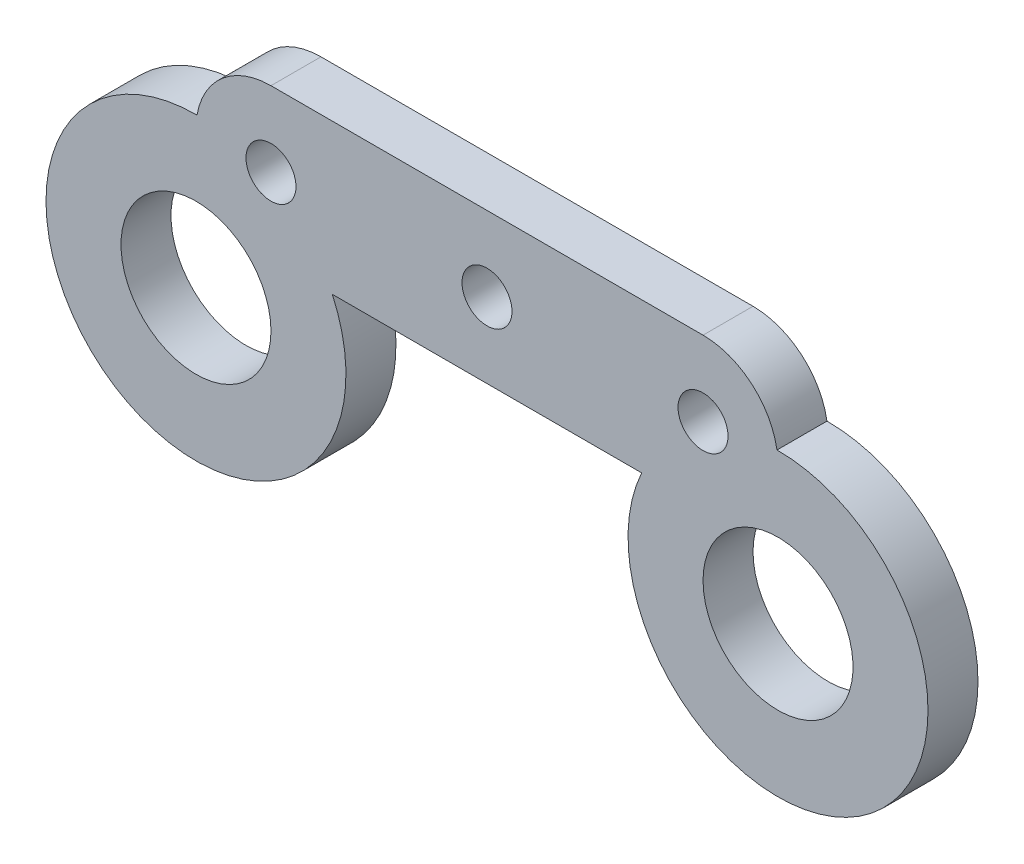
SolidWorks part; units mm, degrees
ref_plane "Front Plane" through (0, 0, 0) normal (0, 0, 1) x (1, 0, 0)
ref_plane "Top Plane" through (0, 0, 0) normal (0, 1, 0) x (1, 0, 0)
ref_plane "Right Plane" through (0, 0, 0) normal (1, 0, 0) x (0, 0, -1)
sketch "Sketch1" plane through (0, 0, 0) normal (0, 0, 1) x (1, 0, 0)
  line L1 (-8.6421, 3) -> (8.6421, 3)
  line L3 (-6.1878, -3) -> (6.1878, -3)
  arc A0 (-11.6002, 0.4999) -> (-6.1878, -3) centre (-11.6421, -5.5) ccw
  circle A5 centre (-11.6421, -5.5) radius 3
  arc A10 (6.1878, -3) -> (11.6002, 0.4999) centre (11.6421, -5.5) ccw
  circle A12 centre (11.6421, -5.5) radius 3
  circle A13 centre (8.6421, 0) radius 1
  arc A14 (8.6421, 3) -> (11.6002, 0.4999) centre (8.6421, 0) cw
  circle A15 centre (-8.6421, 0) radius 1
  arc A16 (-8.6421, 3) -> (-11.6002, 0.4999) centre (-8.6421, 0) ccw
  circle A17 centre (0, 0) radius 1
  dimension "D2" = 6
  dimension "D3" = 2
  dimension "D4" = 2
  dimension "D5" = 2
  dimension "D7" = 12.3756
  dimension "D8" = 6
  dimension "D9" = 6
  dimension "D1" = 6
  dimension "D6" = 17.2843
  dimension "D10" = 8.6421
extrude "Boss-Extrude1" add sketch "Sketch1" along normal blind 2
sketch "Sketch2" plane through (0, -3, 0) normal (0, -1, 0) x (1, 0, 0)
  circle A0 centre (0, 1) radius 0.5
extrude "Cut-Extrude1" cut sketch "Sketch2" against normal blind 0.5
